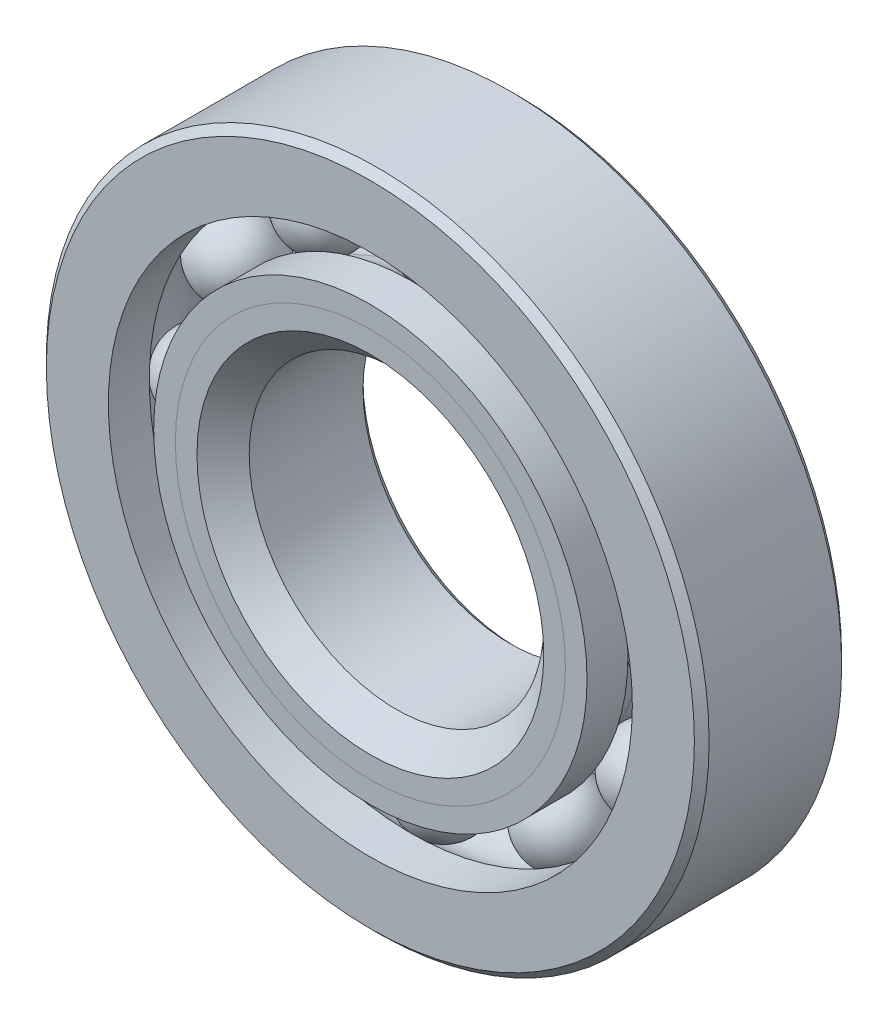
SolidWorks part; units mm, degrees
ref_plane "Front Plane" through (0, 0, 0) normal (0, 0, 1) x (1, 0, 0)
ref_plane "Top Plane" through (0, 0, 0) normal (0, 1, 0) x (1, 0, 0)
ref_plane "Right Plane" through (0, 0, 0) normal (1, 0, 0) x (0, 0, -1)
sketch "Sketch1" plane through (0, 0, 0) normal (1, 0, 0) x (0, 0, -1)
  line L0 (-3.175, 0) -> (3.175, 0) construction
  line L1 (0, 14.2875) -> (0, -14.2875) construction
  line L2 (2.8575, 14.2875) -> (-2.8575, 14.2875)
  line L3 (-2.8575, 14.2875) -> (-3.175, 13.97)
  line L4 (-3.175, 13.97) -> (-3.175, 11.2957)
  line L5 (-3.175, 11.2957) -> (-1.4111, 11.2957)
  line L6 (3.175, 11.2957) -> (1.4111, 11.2957)
  line L7 (3.175, 13.97) -> (3.175, 11.2957)
  line L8 (2.8575, 14.2875) -> (3.175, 13.97)
  line L9 (0, 14.2875) -> (0, 10.3187) construction
  line L10 (0, 10.3187) -> (0, 6.35) construction
  arc A0 (-1.4111, 11.2957) -> (1.4111, 11.2957) centre (0, 10.3187) cw
  point P14 (0, 6.35)
  dimension "Width" = 6.35
  dimension "OD" = 28.575
  dimension "D1" = 45
  dimension "D2" = 0.3175
  dimension "D3" = 2.8222
  dimension "D4" = 0.9769
revolve "Revolve1" add sketch "Sketch1" angle 360 about L0
sketch "Sketch2" plane through (0, 0, 0) normal (1, 0, 0) x (0, 0, -1)
  line L0 (-3.175, 9.3418) -> (-1.4111, 9.3418)
  line L1 (-3.175, 13.97) -> (-3.175, -13.97) construction
  line L2 (-3.175, 9.3418) -> (-3.175, 8.409)
  line L3 (-3.175, 8.409) -> (-2.2422, 7.4762)
  line L4 (-2.2422, 7.4762) -> (0, 7.4762)
  line L5 (0, 14.2875) -> (0, -14.2875) construction
  line L6 (0, 7.4762) -> (0, 8.6025)
  line L7 (0, 8.6025) -> (0, 6.35) construction
  line L8 (-3.175, 9.3418) -> (-3.175, 7.4762) construction
  line L9 (-3.175, 7.4762) -> (-2.2422, 7.4762) construction
  arc A0 (-1.4111, 9.3418) -> (0, 8.6025) centre (0, 10.3187) ccw
  arc A1 (1.4111, 11.2957) -> (-1.4111, 11.2957) centre (0, 10.3187) ccw construction
  circle A2 centre (0, 10.3187) radius 1.7163 construction
  dimension "D1" = 45
revolve "Revolve2" add sketch "Sketch2" angle 360 about L0
sketch "Sketch3" plane through (0, 0, 0) normal (1, 0, 0) x (0, 0, -1)
  line L0 (-3.175, 8.409) -> (-2.2422, 7.4762)
  line L1 (-2.2422, 7.4762) -> (0, 7.4762)
  line L2 (0, 7.4762) -> (0, 8.6025)
  line L3 (-3.175, 8.409) -> (-3.175, 7.4762)
  line L4 (-3.175, 9.3418) -> (-3.175, 7.4762) construction
  line L5 (-3.175, 7.4762) -> (-2.0488, 6.35)
  line L6 (-2.0488, 6.35) -> (2.8575, 6.35)
  line L7 (2.8575, 14.2875) -> (2.8575, -14.2875) construction
  line L8 (2.8575, 6.35) -> (3.175, 6.6675)
  line L9 (3.175, -13.97) -> (3.175, 13.97) construction
  line L10 (3.175, 6.6675) -> (3.175, 9.3418)
  line L11 (3.175, 9.3418) -> (1.4111, 9.3418)
  line L13 (2.8575, 14.2875) -> (3.175, 13.97) construction
  circle A0 centre (0, 10.3187) radius 1.7163 construction
  arc A1 (1.4111, 9.3418) -> (0, 8.6025) centre (0, 10.3187) cw
revolve "Revolve3" add sketch "Sketch3" angle 360 about L0
sketch "Sketch4" plane through (0, 0, 0) normal (1, 0, 0) x (0, 0, -1)
  line L0 (-1.7163, 10.3187) -> (1.7163, 10.3187)
  circle A1 centre (0, 10.3187) radius 1.7163 construction
  arc A2 (-1.7163, 10.3187) -> (1.7163, 10.3187) centre (0, 10.3187) cw
  arc A3 (1.4111, 11.2957) -> (-1.4111, 11.2957) centre (0, 10.3187) ccw construction
revolve "Revolve4" add sketch "Sketch4" angle 360 about L0
ref_axis "Axis1" through (0, 0, -3.175) along (0, 0, 1)
pattern_circular "CirPattern1" count 12 every 30 about axis through (0, 0, -3.175) along (0, 0, 1) of bodies 104
equation "\"D2@Sketch1\" = \"Width@Sketch1\"*.05"
equation "\"D3@Sketch1\" = \"Width@Sketch1\"/2.25"
equation "\"D4@Sketch1\" = (((\"OD@Sketch1\"-\"Width@Sketch1\")/2)/3.25)/3.5"
equation "\"D2@CirPattern1\" = 360/\"Balls@CirPattern1\""
